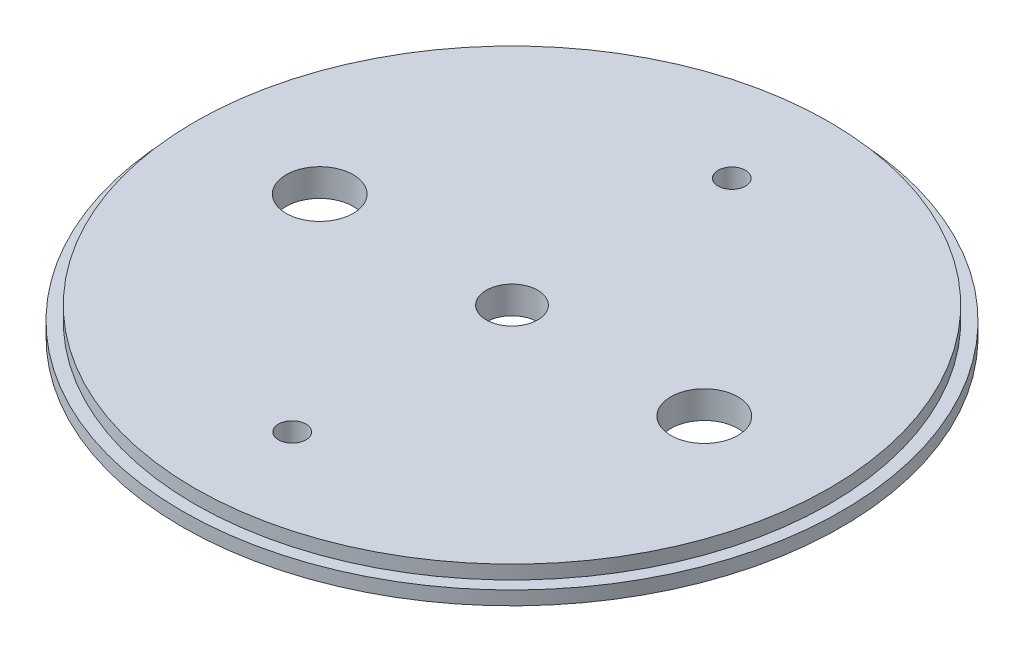
SolidWorks part; units mm, degrees
material "6061-T6 (SS)"
ref_plane "Front Plane" through (0, 0, 0) normal (0, 0, 1) x (1, 0, 0)
ref_plane "Top Plane" through (0, 0, 0) normal (0, 1, 0) x (1, 0, 0)
ref_plane "Right Plane" through (0, 0, 0) normal (1, 0, 0) x (0, 0, -1)
sketch "Sketch1" plane through (0, 0, 0) normal (0, 1, 0) x (1, 0, 0)
  circle A0 centre (0, 0) radius 73.3425
  circle A1 centre (0, 0) radius 76.1746
  dimension "D1" = 146.685
  dimension "D2" = 152.3492
extrude "Boss-Extrude1" add sketch "Sketch1" along normal blind 3.175 contours A0 | A1 A0 region at (0, 0, 0) region at (-74.0201, 0, 0)
extrude "Boss-Extrude2" add sketch "Sketch1<3>" along normal blind 6.35 contours A0 region at (0, 0, 0)
sketch "Sketch1<3>" plane through (0, 0, 0) normal (0, 1, 0) x (1, 0, 0) same geometry as "Sketch1"
sketch "Sketch3" plane through (0, 0, 0) normal (0, -1, 0) x (1, 0, 0)
  line L0 (44.45, 0) -> (-44.45, 0) construction
  line L1 (0, -50.8) -> (0, 50.8) construction
  circle A0 centre (0, 0) radius 5.9531
  circle A1 centre (-44.45, 0) radius 8.25
  circle A2 centre (44.45, 0) radius 8.25
  circle A3 centre (0, 50.8) radius 4.9609
  circle A4 centre (0, -50.8) radius 4.9609
  point P6 (0, 0)
  point P14 (0, 0)
  dimension "D1" = 11.9062
  dimension "D2" = 16.5001
  dimension "D3" = 9.9219
  dimension "D4" = 101.6
  dimension "D5" = 88.9
hole_wizard "1/4 (0.25) Diameter Hole1" positions "Sketch4" profile "Sketch5" hole size "1/4" standard "ANSI Inch" end condition through all
sketch "Sketch4" plane through (0, 0, 0) normal (0, -1, 0) x (-1, 0, 0)
  point P0 (0, 50.8)
  point P3 (0, -50.8)
sketch "Sketch5" plane through (0, 0, -50.8) normal (1, 0, 0) x (0, 0, -1)
  line L0 (0, 0) -> (0, 6.35)
  line L1 (0, 6.35) -> (3.175, 6.35)
  line L2 (3.175, 6.35) -> (3.175, 0)
  line L5 (3.175, 0) -> (0, 0)
  line L11 (0, -6.35) -> (0, 107.95) construction
  dimension "Thru Hole Dia." = 6.35
  dimension "Thru Hole Depth" = 6.35
extrude "Cut-Extrude1" [suppressed] cut sketch "Sketch3" against normal through all
hole_wizard "M18x2.5 Tapped Hole1" positions "Sketch6" profile "Sketch7" tap size "M18x2.5" standard "ANSI Metric" end condition through all
sketch "Sketch6" plane through (0, 0, 0) normal (0, -1, 0) x (-1, 0, 0)
  point P0 (44.45, 0)
  point P3 (-44.45, 0)
sketch "Sketch7" plane through (-44.45, 0, 0) normal (1, 0, 0) x (0, 0, -1)
  line L0 (0, 0) -> (0, 6.35)
  line L1 (0, 6.35) -> (7.75, 6.35)
  line L2 (7.75, 6.35) -> (7.75, 0)
  line L5 (7.75, 0) -> (0, 0)
  line L11 (0, -6.35) -> (0, 107.95) construction
  dimension "Thru Tap Drill Dia." = 15.5
  dimension "Thru Tap Drill Depth" = 6.35
cosmetic thread "Hole Thread1" parameters "D2"=18
cosmetic thread "Hole Thread2" parameters "D2"=18
extrude "Cut-Extrude2" cut sketch "Sketch3<3>" against normal through all contours A0
sketch "Sketch3<3>" plane through (0, 0, 0) normal (0, -1, 0) x (1, 0, 0) same geometry as "Sketch3"
